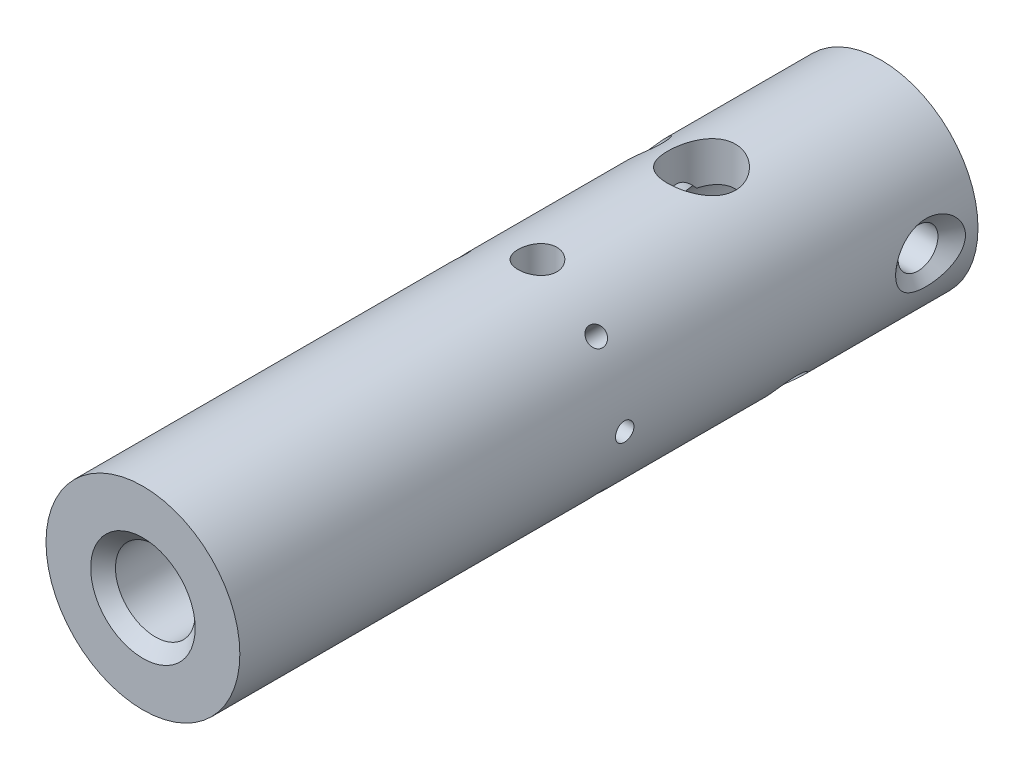
SolidWorks part; units mm, degrees
material "6061-T6 (SS)"
ref_plane "Front Plane" through (0, 0, 0) normal (0, 0, 1) x (1, 0, 0)
ref_plane "Top Plane" through (0, 0, 0) normal (0, 1, 0) x (1, 0, 0)
ref_plane "Right Plane" through (0, 0, 0) normal (1, 0, 0) x (0, 0, -1)
sketch "Sketch1" plane through (0, 0, 0) normal (0, 0, 1) x (1, 0, 0)
  circle A0 centre (0, 0) radius 7.9375
  dimension "D1" = 15.875
extrude "Extrude1" add sketch "Sketch1" along normal mid plane 60.452
sketch "Sketch28" plane through (0, 0, -30.226) normal (0, 0, -1) x (-1, 0, 0)
  line L0 (0, 0) -> (0, 7.9375) construction
  line L1 (0, 0) -> (7.9375, 0) construction
  line L2 (0, 0) -> (5.6127, 5.6127) construction
  circle A0 centre (0, 0) radius 7.9375 construction
hole_wizard "5/16-18 Tapped Hole1" positions "3DSketch1" profile "Sketch2" tap size "5/16-18" standard "Ansi Inch"
sketch3d "3DSketch1"
  line L0 (0, 0, 30.226) -> (0, 0, -30.226) construction
  point P0 (0, 0, 30.226)
sketch "Sketch2" plane through (0, 0, 30.226) normal (1, 0, 0) x (0, -1, 0)
  line L0 (0, 0) -> (0, 27.3611)
  line L1 (0, 27.3611) -> (3.2639, 25.4)
  line L2 (3.2639, 25.4) -> (3.2639, 0)
  line L5 (3.2639, 0) -> (0, 0)
  line L10 (0, 27.3611) -> (-3.2639, 25.4) construction
  line L11 (0, -6.35) -> (0, 107.95) construction
  dimension "Tap Drill Dia." = 6.5278
  dimension "Tap Drill Depth" = 25.4
  dimension "Drill Angle" = 118
chamfer "Chamfer1" distance 1.016 angle 45 1 edges at (3.2639, 0, 30.226)
sketch "Sketch4" plane through (0, 0, -30.226) normal (0, 0, -1) x (-1, 0, 0)
  point P0 (0, 0)
hole_wizard "3/8 (0.375) Diameter Hole1" positions "Sketch8" profile "Sketch7" hole size "3/8" standard "Ansi Inch"
sketch "Sketch8" plane through (0, 0, -30.226) normal (0, 0, -1) x (-1, 0, 0)
  point P1 (0, 0)
sketch "Sketch7" plane through (0, 0, -30.226) normal (1, 0, 0) x (0, 1, 0)
  line L0 (0, 0) -> (0, 39.6916)
  line L1 (0, 39.6916) -> (4.7625, 36.83)
  line L2 (4.7625, 36.83) -> (4.7625, 0)
  line L5 (4.7625, 0) -> (0, 0)
  line L10 (0, 39.6916) -> (-4.7625, 36.83) construction
  line L11 (0, -6.35) -> (0, 107.95) construction
  dimension "Hole Dia." = 9.525
  dimension "Hole Depth" = 36.83
  dimension "Drill Angle" = 118
ref_plane "Plane1" through (7.9375, 0, 0) normal (1, 0, 0) x (0, 0, -1)
sketch "Sketch9" plane through (7.9375, 0, 0) normal (1, 0, 0) x (0, 0, -1)
  line L0 (30.226, 0) -> (26.3398, 0) construction
  line L1 (30.226, -7.9375) -> (30.226, 7.9375) construction
  line L2 (8.7312, 0) -> (-8.7312, 0) construction
  line L3 (26.3398, 0) -> (16.6878, 0) construction
  line L4 (16.6878, 0) -> (15.5194, 0) construction
  line L5 (15.5194, 0) -> (2.0828, 0) construction
  line L6 (2.0828, 0) -> (1.2954, 0) construction
  dimension "D1" = 3.8862
  dimension "D2" = 13.5382
  dimension "D3" = 14.7066
  dimension "D4" = 28.1432
  dimension "D5" = 28.9306
hole_wizard "CSK for #4 Flat Head Machine Screw (100)1" positions "Sketch18" profile "Sketch17" countersink size "#4" standard "Ansi Inch" end condition through all
sketch "Sketch18" plane through (7.9375, 0, 0) normal (1, 0, 0) x (0, 0, -1)
  point P1 (26.3398, 0)
sketch "Sketch17" plane through (7.9375, 0, -26.3398) normal (0, 1, 0) x (0, 0, -1)
  line L0 (0, 0) -> (0, 15.875)
  line L1 (0, 15.875) -> (1.6319, 15.875)
  line L2 (1.6319, 15.875) -> (1.6319, 1.0284)
  line L3 (1.6319, 1.0284) -> (2.8575, 0)
  line L5 (2.8575, 0) -> (0, 0)
  line L6 (-1.6319, 1.0284) -> (-2.8575, 0) construction
  line L11 (0, -6.35) -> (0, 107.95) construction
  dimension "Thru Hole Dia." = 3.2639
  dimension "Thru Hole Depth" = 15.875
  dimension "Near C'Sink Dia." = 5.715
  dimension "Near C'Sink Angle" = 100
hole_wizard "#53 (0.0595) Diameter Hole1" positions "Sketch21" profile "Sketch22" hole size "#53" standard "Ansi Inch" end condition through all
sketch "Sketch21" plane through (7.9375, 0, 0) normal (1, 0, 0) x (0, 0, -1)
  point P4 (1.2954, 0)
sketch "Sketch22" plane through (7.9375, 0, -1.2954) normal (0, 1, 0) x (0, 0, -1)
  line L0 (0, 0) -> (0, 19.1628)
  line L1 (0, 19.1628) -> (0.7556, 19.1628)
  line L2 (0.7556, 19.1628) -> (0.7556, 0)
  line L5 (0.7556, 0) -> (0, 0)
  line L11 (0, -6.35) -> (0, 107.95) construction
  dimension "Thru Hole Dia." = 1.5113
  dimension "Thru Hole Depth" = 19.1628
pattern_circular "CirPattern1" count 4 every 45 about axis through (0, 0, 30.226) along (0, 0, -1) of "#53 (0.0595) Diameter Hole1"
ref_plane "Plane3" through (0, 7.9375, -30.226) normal (0, 1, 0) x (-1, 0, 0)
sketch "Sketch29" plane through (0, 7.9375, -30.226) normal (0, 1, 0) x (-1, 0, 0)
  line L0 (0, 0) -> (0, 14.7066) construction
  line L1 (0, 0) -> (0, 28.1432) construction
  line L2 (0, 60.452) -> (0, 0) construction
  dimension "D1" = 14.7066
  dimension "D2" = 28.1432
hole_wizard "7/32 (0.21875) Diameter Hole1" positions "Sketch32" profile "Sketch31" hole size "7/32" standard "Ansi Inch"
sketch "Sketch32" plane through (0, 7.9375, -30.226) normal (0, 1, 0) x (-1, 0, 0)
  point P1 (0, 14.7066)
sketch "Sketch31" plane through (0, 7.9375, -15.5194) normal (1, 0, 0) x (0, 0, 1)
  line L0 (0, 0) -> (0, 17.6713)
  line L1 (0, 17.6713) -> (2.7781, 16.002)
  line L2 (2.7781, 16.002) -> (2.7781, 0)
  line L5 (2.7781, 0) -> (0, 0)
  line L10 (0, 17.6713) -> (-2.7781, 16.002) construction
  line L11 (0, -6.35) -> (0, 107.95) construction
  dimension "Hole Dia." = 5.5562
  dimension "Hole Depth" = 16.002
  dimension "Drill Angle" = 118
ref_plane "Plane4" through (-5.6127, 5.6127, -30.226) normal (-0.7071, 0.7071, 0) x (-0.7071, -0.7071, 0)
sketch "Sketch33" plane through (-5.6127, 5.6127, -30.226) normal (-0.7071, 0.7071, 0) x (-0.7071, -0.7071, 0)
  line L0 (0, 0) -> (0, 13.5382) construction
  dimension "D1" = 13.5382
hole_wizard "1/8 (0.125) Diameter Hole8" positions "Sketch35" profile "Sketch34" hole size "1/8" standard "Ansi Inch" end condition through all
sketch "Sketch35" plane through (-5.6127, 5.6127, -30.226) normal (-0.7071, 0.7071, 0) x (-0.7071, -0.7071, 0)
  point P1 (0, 13.5382)
sketch "Sketch34" plane through (-5.6127, 5.6127, -16.6878) normal (0, 0, 1) x (-0.7071, -0.7071, 0)
  line L0 (0, 0) -> (0, 19.1628)
  line L1 (0, 19.1628) -> (1.5875, 19.1628)
  line L2 (1.5875, 19.1628) -> (1.5875, 0)
  line L5 (1.5875, 0) -> (0, 0)
  line L11 (0, -6.35) -> (0, 107.95) construction
  dimension "Thru Hole Dia." = 3.175
  dimension "Thru Hole Depth" = 19.1628
hole_wizard "1/8 (0.125) Diameter Hole9" positions "Sketch38" profile "Sketch37" hole size "1/8" standard "Ansi Inch"
sketch "Sketch38" plane through (0, 7.9375, -30.226) normal (0, 1, 0) x (-1, 0, 0)
  point P1 (0, 28.1432)
sketch "Sketch37" plane through (0, 7.9375, -2.0828) normal (1, 0, 0) x (0, 0, 1)
  line L0 (0, 0) -> (0, 16.9559)
  line L1 (0, 16.9559) -> (1.5875, 16.002)
  line L2 (1.5875, 16.002) -> (1.5875, 0)
  line L5 (1.5875, 0) -> (0, 0)
  line L10 (0, 16.9559) -> (-1.5875, 16.002) construction
  line L11 (0, -6.35) -> (0, 107.95) construction
  dimension "Hole Dia." = 3.175
  dimension "Hole Depth" = 16.002
  dimension "Drill Angle" = 118
